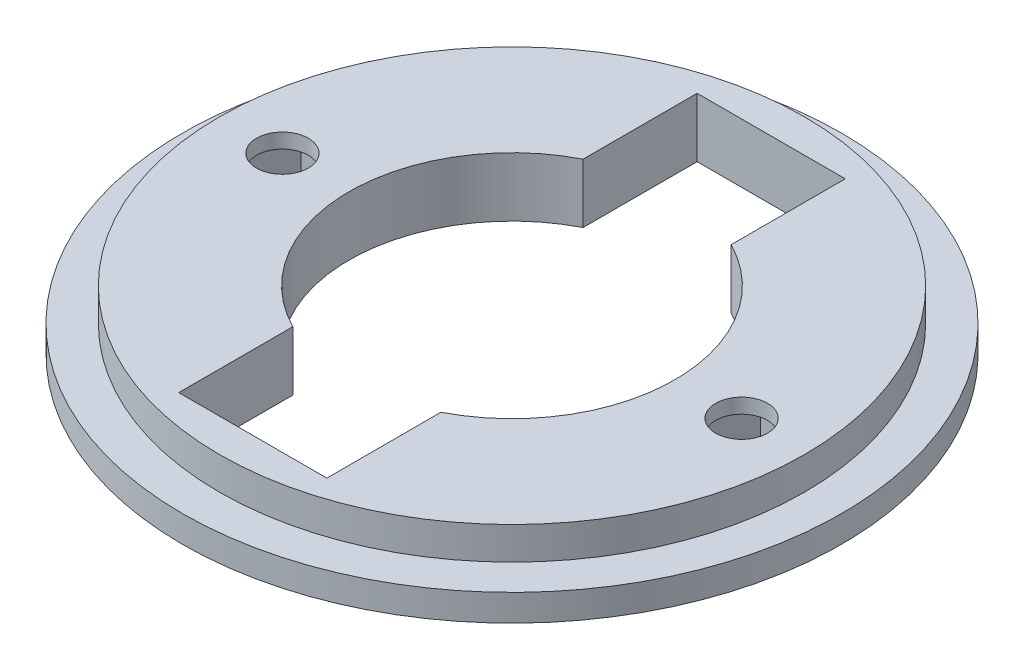
SolidWorks part; units mm, degrees
ref_plane "Front Plane" through (0, 0, 0) normal (0, 0, 1) x (1, 0, 0)
ref_plane "Top Plane" through (0, 0, 0) normal (0, 1, 0) x (1, 0, 0)
ref_plane "Right Plane" through (0, 0, 0) normal (1, 0, 0) x (0, 0, -1)
sketch "Sketch1" plane through (0, 0, 0) normal (0, 1, 0) x (1, 0, 0)
  circle A0 centre (0, 0) radius 22.25
  dimension "D1" = 44.5
extrude "Boss-Extrude2" add sketch "Sketch1" along normal blind 4
sketch "Sketch2" plane through (0, 4, 0) normal (0, 1, 0) x (1, 0, 0)
  circle A0 centre (0, 0) radius 19.75
  circle A1 centre (0, 0) radius 22.25
  dimension "D1" = 39.5
  dimension "D2" = 44.5
extrude "Cut-Extrude1" cut sketch "Sketch2" against normal blind 2.2
sketch "Sketch3" plane through (0, 4, 0) normal (0, 1, 0) x (1, 0, 0)
  line L0 (5, -9.798) -> (5, -17.5)
  line L1 (-5, 17.5) -> (5, 17.5)
  line L2 (-5, 17.5) -> (-5, 9.798)
  line L3 (-5, -17.5) -> (5, -17.5)
  line L4 (5, 17.5) -> (5, 9.798)
  line L5 (-5, 17.5) -> (5, -17.5) construction
  line L6 (-5, -17.5) -> (5, 17.5) construction
  line L7 (-5, -9.798) -> (-5, -17.5)
  arc A0 (-5, 9.798) -> (-5, -9.798) centre (0, 0) ccw
  arc A1 (5, -9.798) -> (5, 9.798) centre (0, 0) ccw
  point P0 (0, 0)
  dimension "D3" = 22
  dimension "D1" = 35
  dimension "D2" = 10
extrude "Cut-Extrude2" cut sketch "Sketch3" against normal through all
sketch "Sketch4" plane through (0, 4, 0) normal (0, 1, 0) x (1, 0, 0)
  line L0 (0, 0) -> (24.6184, 0) construction
  line L1 (0, 0) -> (0, -30.6196) construction
  circle A0 centre (15.5, 0) radius 1.75
  circle A3 centre (-15.5, 0) radius 1.75
  dimension "D1" = 3.5
  dimension "D3" = 31
extrude "Cut-Extrude3" cut sketch "Sketch4" against normal through all
sketch "Sketch5" plane through (0, 0, 0) normal (0, -1, 0) x (1, 0, 0)
  line L0 (0, 0) -> (-24.2775, 0) construction
  line L1 (0, 0) -> (0, 27.2098) construction
  line L2 (13.7679, -3) -> (12.0359, 0)
  line L3 (-12.0359, 0) -> (-13.7679, 3)
  line L4 (-13.7679, 3) -> (-17.2321, 3)
  line L5 (-17.2321, 3) -> (-18.9641, 0)
  line L6 (-18.9641, 0) -> (-17.2321, -3)
  line L7 (-17.2321, -3) -> (-13.7679, -3)
  line L8 (-13.7679, -3) -> (-12.0359, 0)
  line L9 (17.2321, -3) -> (13.7679, -3)
  line L10 (18.9641, 0) -> (17.2321, -3)
  line L11 (17.2321, 3) -> (18.9641, 0)
  line L12 (13.7679, 3) -> (17.2321, 3)
  line L13 (12.0359, 0) -> (13.7679, 3)
  circle A0 centre (-15.5, 0) radius 3 construction
  circle A1 centre (15.5, 0) radius 3 construction
  dimension "D1" = 6
extrude "Cut-Extrude4" cut sketch "Sketch5" against normal blind 3
